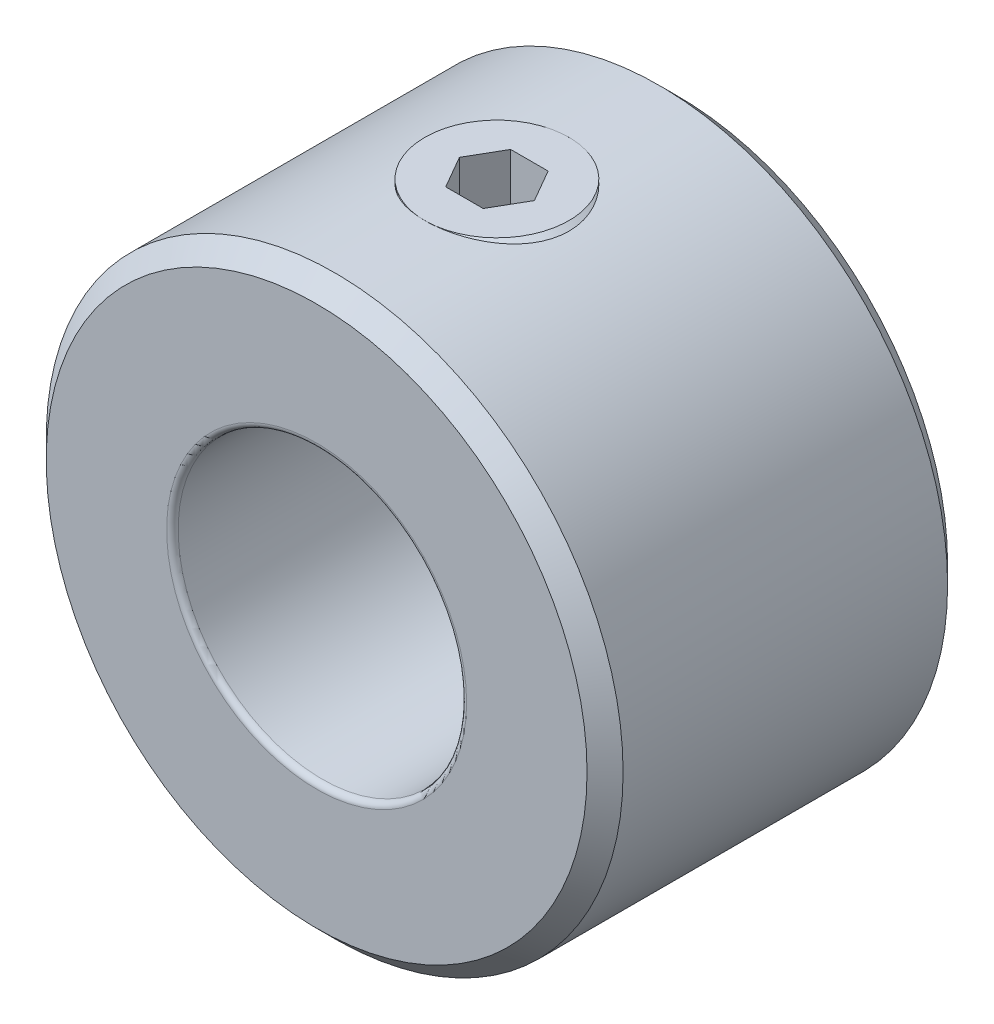
SolidWorks part; units mm, degrees
ref_plane "Front Plane" through (0, 0, 0) normal (0, 0, 1) x (1, 0, 0)
ref_plane "Top Plane" through (0, 0, 0) normal (0, 1, 0) x (1, 0, 0)
ref_plane "Right Plane" through (0, 0, 0) normal (1, 0, 0) x (0, 0, -1)
sketch "Sketch1" plane through (0, 0, 0) normal (0, 0, 1) x (1, 0, 0)
  line L0 (0, 4) -> (0, 0) construction
  line L1 (0, 0) -> (-2.8284, -2.8284) construction
  circle A0 centre (0, 0) radius 4
  circle A1 centre (0, 0) radius 2
  point P4 (4, 0)
  point P5 (0, 4)
  dimension "Bore Dia" = 4
  dimension "OD" = 8
  dimension "D1" = 135
extrude "Extrude1" add sketch "Sketch1" along normal blind 5
ref_plane "Plane1" through (0, 4, 0) normal (0, 1, 0) x (-1, 0, 0)
sketch "Sketch2" plane through (0, 4, 0) normal (0, 1, 0) x (-1, 0, 0)
  line L0 (0, 0) -> (0, 5) construction
  line L2 (4, 5) -> (-4, 5) construction
  circle A0 centre (0, 2.5) radius 1
  point P8 (0, 2.5)
  dimension "Set Screw Dia" = 2
extrude "Cut-Extrude1" cut sketch "Sketch2" against normal up to surface (4 mm away) up to plane "Top Plane"
ref_plane "Plane2" through (0, 0, 2.5) normal (0, 0, 1) x (1, 0, 0)
sketch "Sketch3" plane through (0, 0, 2.5) normal (0, 0, 1) x (1, 0, 0)
  line L0 (-0.9, 4) -> (-1, 3.93)
  line L1 (0, 1.3293) -> (0, 4)
  line L3 (-1, 1.452) -> (-1, 3.93)
  line L4 (0, 4) -> (-0.9, 4)
  line L5 (0, 1) -> (0, 0) construction
  line L6 (-1, 3.93) -> (0, 3.93) construction
  line L7 (0, 1.3293) -> (-0.548, 1)
  line L8 (-0.548, 1) -> (-1, 1.452)
  point P1 (-0.548, 1)
  dimension "Screw Length" = 3
  dimension "D3" = 2
  dimension "D1" = 1.8
  dimension "D7" = 1
  dimension "D2" = 35
  dimension "D4" = 59
  dimension "D5" = 45
revolve "Revolve1" add sketch "Sketch3" angle 360 about L1
sketch "Sketch4" plane through (0, 4, 0) normal (0, 1, 0) x (0, 0, -1)
  line L0 (-2.5, 0.5196) -> (-2.5, -0.5196) construction
  line L1 (-2.5, 0.5196) -> (-2.95, 0.2598)
  line L2 (-2.95, 0.2598) -> (-2.95, -0.2598)
  line L3 (-2.95, -0.2598) -> (-2.5, -0.5196)
  line L4 (-2.5, -0.5196) -> (-2.05, -0.2598)
  line L5 (-2.05, -0.2598) -> (-2.05, 0.2598)
  line L6 (-2.05, 0.2598) -> (-2.5, 0.5196)
  circle A0 centre (-2.5, 0) radius 0.45 construction
  circle A1 centre (-2.5, 0) radius 0.5196 construction
  dimension "D1" = 1.0392
  dimension "Hex" = 0.9
extrude "Cut-Extrude2" cut sketch "Sketch4" against normal blind 0.72
fillet "Fillet1" radius 0.08 2 edges at (2, 0, 0) (2, 0, 5)
chamfer "Chamfer1" distance 0.25 angle 45 2 edges at (4, 0, 5) (4, 0, 0)
sketch "Sketch5" plane through (0, 4, 0) normal (0, 1, 0) x (1, 0, 0)
  circle A0 centre (0, -2.5) radius 1 construction
  circle A1 centre (0, -2.5) radius 1
curve "Helix/Spiral1" pitch 0.4 height 3 radius 1 centre (0, 4, 2.5) axis (0, -1, 0) start towards (-1, 0, 0) parameters "Pitch"=0.4
ref_plane "Plane3" through (0, 0, 2.5) normal (0, 0, 1) x (1, 0, 0)
sketch "Sketch9" plane through (0, 0, 2.5) normal (0, 0, 1) x (1, 0, 0)
  line L0 (-1, 4) -> (-1, 4.35)
  line L1 (-1, 4.35) -> (-0.7402, 4.2)
  line L2 (-0.7402, 4.2) -> (-0.7402, 4.15)
  line L3 (-0.7402, 4.15) -> (-1, 4)
  line L4 (-1, 4.175) -> (-0.7402, 4.175) construction
  line L5 (-0.8701, 4.075) -> (-0.8701, 4.275) construction
  dimension "D1" = 0.05
  dimension "D2" = 0.2
  dimension "D3" = 60
sweep "Cut-Sweep2" cut profiles "Sketch9" path "Helix/Spiral1" align with end faces yes
sketch "Sketch10" plane through (0, 4, 0) normal (0, 1, 0) x (1, 0, 0)
  line L0 (-0.2598, -2.05) -> (-0.5196, -2.5) construction
  line L1 (-0.5196, -2.5) -> (-0.2598, -2.95) construction
  line L2 (-0.2598, -2.95) -> (0.2598, -2.95) construction
  line L3 (0.2598, -2.95) -> (0.5196, -2.5) construction
  line L4 (0.5196, -2.5) -> (0.2598, -2.05) construction
  line L5 (0.2598, -2.05) -> (-0.2598, -2.05) construction
  line L6 (-0.2598, -2.05) -> (-0.5196, -2.5)
  line L7 (-0.5196, -2.5) -> (-0.2598, -2.95)
  line L8 (-0.2598, -2.95) -> (0.2598, -2.95)
  line L9 (0.2598, -2.95) -> (0.5196, -2.5)
  line L10 (0.5196, -2.5) -> (0.2598, -2.05)
  line L11 (0.2598, -2.05) -> (-0.2598, -2.05)
  circle A0 centre (0, -2.5) radius 1 construction
  circle A1 centre (0, -2.5) radius 1
extrude "Boss-Extrude1" add sketch "Sketch10" against normal through all draft 60
ref_plane "Contact Plane 1" through (0, 0, 5) normal (0, 0, 1) x (1, 0, 0)
ref_plane "Contact Plane 2" through (0, 0, 0) normal (0, 0, -1) x (-1, 0, 0)
ref_plane "Contact Plane 3" through (0, 1, 0) normal (0, -1, 0) x (-1, 0, 0)
ref_axis "Central Axis 1" through (0, 0, 4.92) along (0, 0, -1)
equation "\"D1@Fillet1\" = \"OD@Sketch1\"*.01"
equation "\"D1@Cut-Extrude2\" = \"Hex@Sketch4\"*.8"
equation "\"D3@Sketch3\"=\"Set Screw Dia@Sketch2\""
equation "\"D1@Sketch3\"=\"Set Screw Dia@Sketch2\"*.9"
equation "\"D3@Helix/Spiral1\"=\"Screw Length@Sketch3\""
equation "\"D1@Sketch9\"=\"Pitch@Helix/Spiral1\"*.125"
equation "\"D2@Sketch9\"=\"Pitch@Helix/Spiral1\"*.50"
